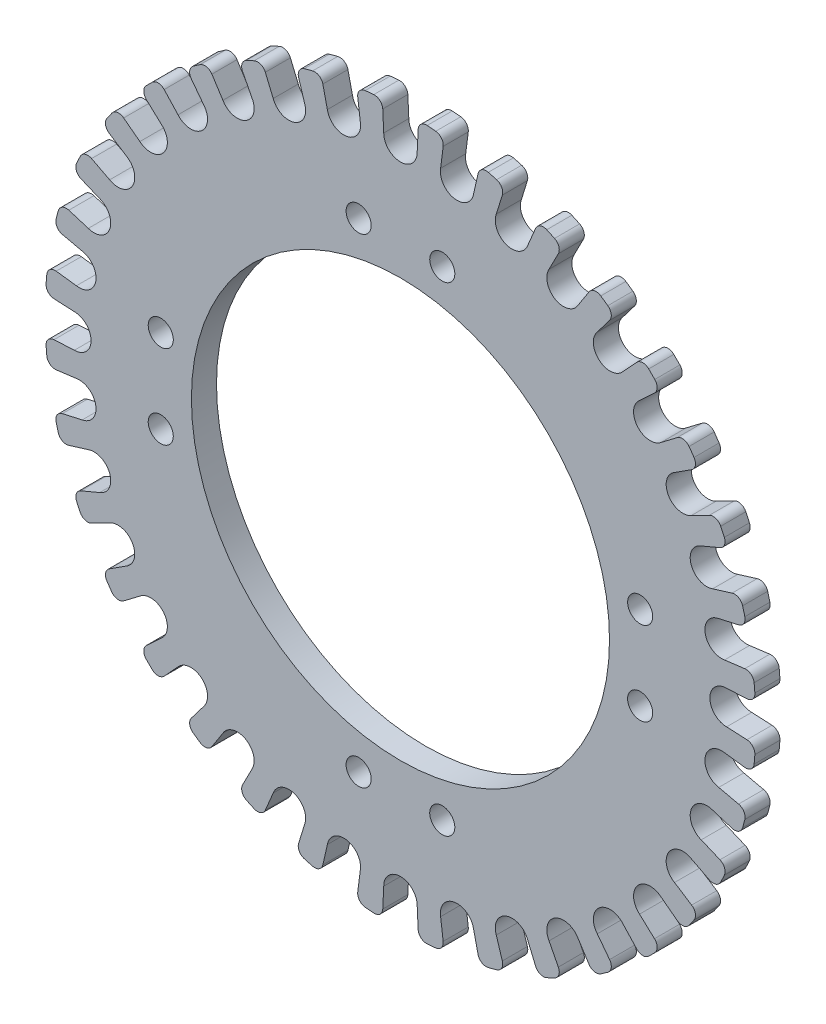
SolidWorks part; units mm, degrees
ref_plane "Front Plane" through (0, 0, 0) normal (0, 0, 1) x (1, 0, 0)
ref_plane "Top Plane" through (0, 0, 0) normal (0, 1, 0) x (1, 0, 0)
ref_plane "Right Plane" through (0, 0, 0) normal (1, 0, 0) x (0, 0, -1)
sketch "Sketch1" plane through (0, 0, 0) normal (0, 0, 1) x (1, 0, 0)
  line L0 (0, 0) -> (0, 76.7228) construction
  line L1 (-5, 28.6654) -> (7.5438, 28.6654) construction
  line L2 (-1.65, 27.0934) -> (1.65, 27.0934) construction
  line L3 (-1.65, 27.0934) -> (-1.65, 38.3614) construction
  line L4 (-1.65, 38.3614) -> (1.65, 38.3614) construction
  line L5 (1.65, 27.0934) -> (1.65, 38.3614) construction
  circle A0 centre (0, 0) radius 42.5
  circle A1 centre (0, 0) radius 25
  circle A2 centre (-5, 28.6654) radius 1.5
  circle A3 centre (5, 28.6654) radius 1.5
  circle A4 centre (28.6654, 5) radius 1.5
  circle A5 centre (28.6654, -5) radius 1.5
  circle A6 centre (5, -28.6654) radius 1.5
  circle A7 centre (-5, -28.6654) radius 1.5
  circle A8 centre (-28.6654, -5) radius 1.5
  circle A9 centre (-28.6654, 5) radius 1.5
  point P7 (0, 42.5)
  point P10 (0, 38.3614)
  dimension "D1" = 85
  dimension "D2" = 50
  dimension "D3" = 3
  dimension "D4" = 3.3
  dimension "D5" = 5
  dimension "D6" = 4
extrude "Boss-Extrude1" add sketch "Sketch1" along normal blind 3
sketch "Sketch2" plane through (0, 0, 3) normal (0, 0, 1) x (1, 0, 0)
  line L0 (0, 0) -> (0, 46.0615) construction
  line L1 (-2, 39) -> (-2.25, 44.1517)
  line L2 (-2.25, 44.1517) -> (2.25, 44.1517)
  line L3 (2.25, 44.1517) -> (2, 39)
  arc A0 (-2, 39) -> (2, 39) centre (0, 39) ccw
  circle A1 centre (0, 0) radius 42.5 construction
  point P4 (0, 44.1517)
  point P5 (0, 42.5)
  dimension "D1" = 3.5
  dimension "D3" = 2.25
  dimension "D2" = 2
extrude "Cut-Extrude1" cut sketch "Sketch2" against normal through all
sketch "Sketch5" plane through (0, 0, 3) normal (0, 0, 1) x (1, 0, 0)
  line L0 (3.8898, 40.5) -> (-1.3229, 40.5) construction
  line L1 (0, 42.5) -> (3.8939, 42.5) construction
  line L4 (-2, 39) -> (-2.1672, 42.4447)
  line L5 (-2, 39) -> (-2.1672, 42.4447)
  line L6 (2.1672, 42.4447) -> (2, 39)
  line L7 (2.1672, 42.4447) -> (2, 39)
  circle A0 centre (0, 39) radius 2 construction
  circle A1 centre (0, 0) radius 42.5 construction
  arc A3 (-2.1672, 42.4447) -> (2.1672, 42.4447) centre (0, 0) ccw
  arc A4 (-2.1672, 42.4447) -> (2.1672, 42.4447) centre (0, 0) ccw
  arc A194 (-2, 39) -> (2, 39) centre (0, 39) ccw
  arc A195 (-2, 39) -> (2, 39) centre (0, 39) ccw
  dimension "D1" = 0
  dimension "D2" = 2
fillet "Fillet1" radius 1 2 edges at (-2.1672, 42.4447, 1.5) (2.1672, 42.4447, 1.5)
pattern_circular "CirPattern1" count 36 over 360 about axis through (0, 0, 3) along (0, 0, -1) of "Fillet1", "Cut-Extrude1" reverse direction yes
